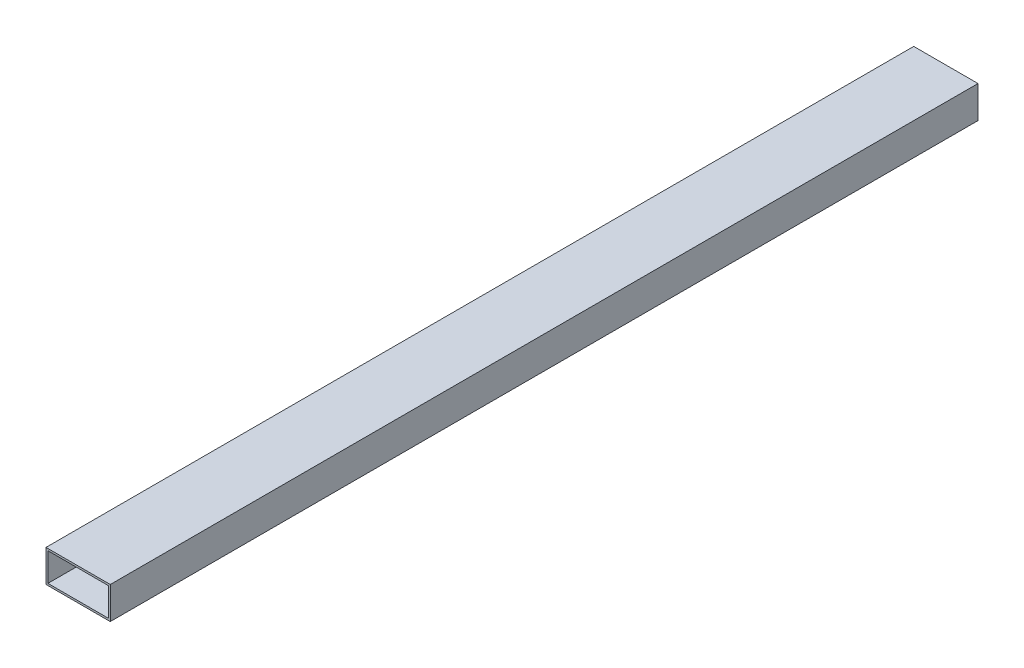
SolidWorks part; units mm, degrees
ref_plane "Front Plane" through (0, 0, 0) normal (0, 0, 1) x (1, 0, 0)
ref_plane "Top Plane" through (0, 0, 0) normal (0, 1, 0) x (1, 0, 0)
ref_plane "Right Plane" through (0, 0, 0) normal (1, 0, 0) x (0, 0, -1)
sketch "Sketch2" plane through (0, 0, 0) normal (0, 0, 1) x (1, 0, 0)
  line L1 (0, 0) -> (-50.8, 0)
  line L2 (0, 0) -> (0, 25.4)
  line L3 (0, 25.4) -> (-50.8, 25.4)
  line L4 (-50.8, 0) -> (-50.8, 25.4)
  dimension "D1" = 50.8
  dimension "D2" = 25.4
extrude "Extrude-Thin1" add sketch "Sketch2" along normal blind 685.8 thin thin type one direction reverse wall 1.524
